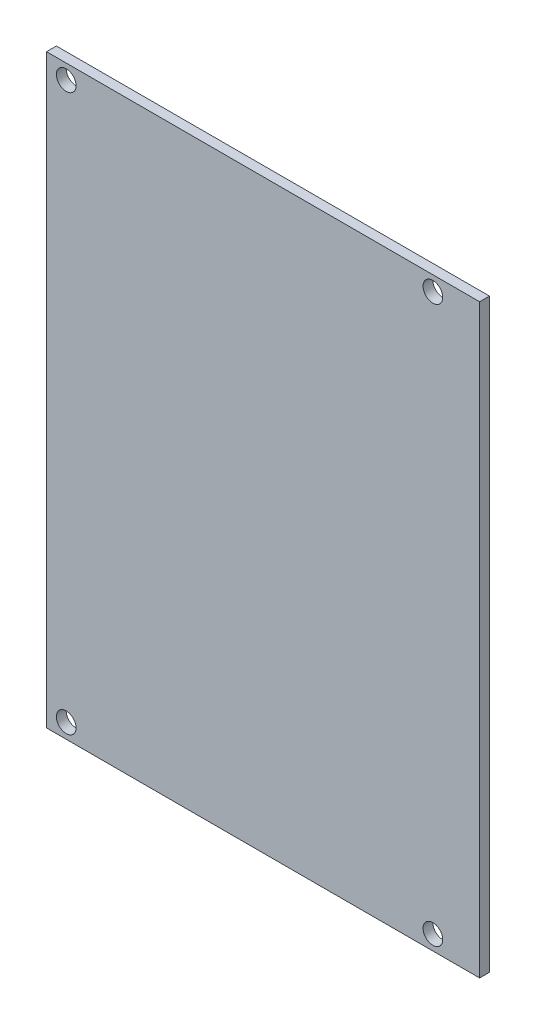
SolidWorks part; units mm, degrees
ref_plane "Plan de face" through (0, 0, 0) normal (0, 0, 1) x (1, 0, 0)
ref_plane "Plan de dessus" through (0, 0, 0) normal (0, 1, 0) x (1, 0, 0)
ref_plane "Plan de droite" through (0, 0, 0) normal (1, 0, 0) x (0, 0, -1)
sketch "Main-Sketch" plane through (0, 0, 0) normal (0, 0, 1) x (1, 0, 0)
  line L1 (0, 0) -> (88, 0)
  line L2 (0, 0) -> (0, 119)
  line L3 (0, 119) -> (88, 119)
  line L4 (88, 0) -> (88, 119)
  dimension "D1" = 88
  dimension "D2" = 119
extrude "Main-Extrusion" add sketch "Main-Sketch" along normal blind 2
sketch "Fix-Sketch" plane through (0, 0, 2) normal (0, 0, 1) x (1, 0, 0)
  line L0 (88, 119) -> (0, 119) construction
  line L2 (0, 119) -> (0, 0) construction
  line L3 (0, 0) -> (88, 0) construction
  circle A0 centre (4, 116) radius 2
  circle A1 centre (4, 3) radius 2
  circle A2 centre (78.5, 3) radius 2
  circle A3 centre (78.5, 116) radius 2
  dimension "D1" = 3
  dimension "D2" = 4
  dimension "D4" = 4
  dimension "D5" = 3
  dimension "D6" = 74.5
extrude "Fix-Hole" cut sketch "Fix-Sketch" against normal through all
